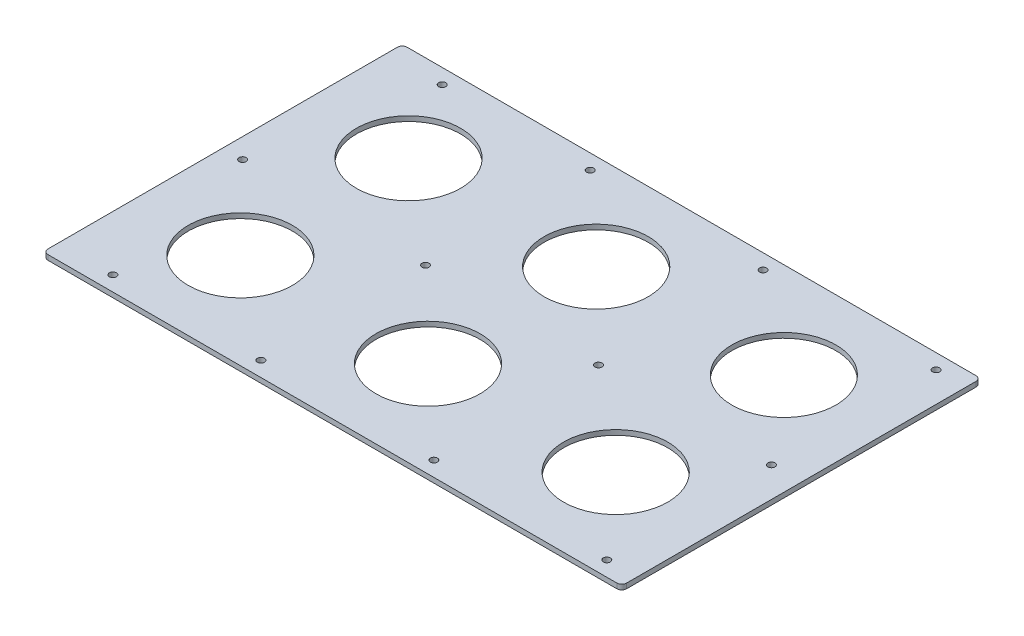
SolidWorks part; units mm, degrees
material "ABS"
ref_plane "Front" through (0, 0, 0) normal (0, 0, 1) x (1, 0, 0)
ref_plane "Top" through (0, 0, 0) normal (0, 1, 0) x (1, 0, 0)
ref_plane "Right" through (0, 0, 0) normal (1, 0, 0) x (0, 0, -1)
sketch "Sketch1" plane through (0, 0, 0) normal (0, 1, 0) x (1, 0, 0)
  line L1 (-180.975, 114.3) -> (180.975, 114.3)
  line L2 (-184.15, 111.125) -> (-184.15, -111.125)
  line L3 (-180.975, -114.3) -> (180.975, -114.3)
  line L4 (184.15, 111.125) -> (184.15, -111.125)
  line L5 (-184.15, 114.3) -> (184.15, -114.3) construction
  line L6 (-184.15, -114.3) -> (184.15, 114.3) construction
  circle A0 centre (119.5086, -53.5178) radius 33.147
  arc A1 (-184.15, -111.125) -> (-180.975, -114.3) centre (-180.975, -111.125) ccw
  arc A2 (180.975, -114.3) -> (184.15, -111.125) centre (180.975, -111.125) ccw
  arc A3 (184.15, 111.125) -> (180.975, 114.3) centre (180.975, 111.125) ccw
  arc A4 (-180.975, 114.3) -> (-184.15, 111.125) centre (-180.975, 111.125) ccw
  circle A5 centre (165.1, 0) radius 2.2479 construction
  circle A6 centre (165.1, 0) radius 2.2479
  circle A7 centre (-171.45, 0) radius 2.2479 construction
  circle A8 centre (-171.45, 0) radius 2.2479
  circle A21 centre (-55.0333, 0) radius 2.2479 construction
  circle A22 centre (55.0333, 0) radius 2.2479 construction
  circle A23 centre (-55.0333, 0) radius 2.2479
  circle A24 centre (55.0333, 0) radius 2.2479
  circle A25 centre (119.5086, 53.5178) radius 33.147
  circle A26 centre (0.0643, 53.5178) radius 33.147
  circle A27 centre (0.0643, -53.5178) radius 33.147
  circle A28 centre (-119.38, 53.5178) radius 33.147
  circle A29 centre (-119.38, -53.5178) radius 33.147
  arc A34 (-143.7521, 103.8733) -> (-143.7521, 3.1623) centre (-119.38, 53.5178) ccw construction
  arc A35 (-24.3078, 103.8733) -> (-24.3078, 3.1623) centre (0.0643, 53.5178) ccw construction
  arc A36 (95.1365, 103.8733) -> (95.1365, 3.1623) centre (119.5086, 53.5178) ccw construction
  arc A37 (-143.7521, -3.1623) -> (-143.7521, -103.8733) centre (-119.38, -53.5178) ccw construction
  arc A38 (-24.3078, -3.1623) -> (-24.3078, -103.8733) centre (0.0643, -53.5178) ccw construction
  arc A39 (95.1365, -3.1623) -> (95.1365, -103.8733) centre (119.5086, -53.5178) ccw construction
  circle A40 centre (-149.225, -104.775) radius 2.2479 construction
  circle A41 centre (-55.0333, -104.775) radius 2.2479 construction
  circle A42 centre (55.0333, -104.775) radius 2.2479 construction
  circle A43 centre (165.1, -104.775) radius 2.2479 construction
  circle A44 centre (-149.225, 104.775) radius 2.2479 construction
  circle A45 centre (-55.0333, 104.775) radius 2.2479 construction
  circle A46 centre (55.0333, 104.775) radius 2.2479 construction
  circle A47 centre (165.1, 104.775) radius 2.2479 construction
  circle A48 centre (-149.225, -104.775) radius 2.2479
  circle A49 centre (-55.0333, -104.775) radius 2.2479
  circle A50 centre (55.0333, -104.775) radius 2.2479
  circle A51 centre (165.1, -104.775) radius 2.2479
  circle A52 centre (-149.225, 104.775) radius 2.2479
  circle A53 centre (-55.0333, 104.775) radius 2.2479
  circle A54 centre (55.0333, 104.775) radius 2.2479
  circle A55 centre (165.1, 104.775) radius 2.2479
  point P0 (0, 0)
  dimension "D3" = 66.294
  dimension "D4" = 3.175
  dimension "D1" = 368.3
  dimension "D2" = 228.6
extrude "Boss-Extrude1" add sketch "Sketch1" along normal blind 3.175
sketch "Sketch2" [suppressed] plane through (0, 3.175, 0) normal (0, 1, 0) x (1, 0, 0)
  line L0 (170.15, 30) -> (170.15, -30) construction
  line L1 (0, 0) -> (184.15, 0) construction
  line L2 (184.15, -111.125) -> (184.15, 111.125) construction
  text T0 "W" font "Stencil" height in points 30
  point P7 (170.15, 0)
  dimension "D1" = 14
  dimension "D2" = 60
extrude "Cut-Extrude1" [suppressed] cut sketch "Sketch2" against normal through all
sketch "Sketch3" [suppressed] plane through (0, 0, 0) normal (0, 1, 0) x (1, 0, 0)
  line L0 (564.5895, -114.2759) -> (564.5895, 114.3581)
  line L1 (-186.5909, 117.2946) -> (1032.6091, 117.2946)
  line L2 (-186.5909, 117.2946) -> (-186.5909, -492.3054)
  line L3 (-186.5909, -492.3054) -> (1032.6091, -492.3054)
  line L4 (1032.6091, 117.2946) -> (1032.6091, -492.3054)
  line L5 (184.5895, -114.2759) -> (-184.2953, -114.2759)
  line L6 (184.5895, -114.2759) -> (184.5895, 114.3581)
  line L7 (184.5895, 114.3581) -> (-184.2953, 114.3581)
  line L8 (-184.2953, -114.2759) -> (-184.2953, 114.3581)
  line L9 (564.5895, -114.2759) -> (195.7047, -114.2759)
  line L10 (195.7047, -114.2759) -> (195.7047, 114.3581)
  line L11 (564.5895, 114.3581) -> (195.7047, 114.3581)
  line L12 (944.5895, -114.2759) -> (944.5895, 114.3581)
  line L13 (944.5895, -114.2759) -> (575.7047, -114.2759)
  line L14 (575.7047, -114.2759) -> (575.7047, 114.3581)
  line L15 (944.5895, 114.3581) -> (575.7047, 114.3581)
  line L16 (564.5895, -364.2759) -> (564.5895, -135.6419)
  line L17 (564.5895, -364.2759) -> (195.7047, -364.2759)
  line L18 (195.7047, -364.2759) -> (195.7047, -135.6419)
  line L19 (564.5895, -135.6419) -> (195.7047, -135.6419)
  line L20 (944.5895, -364.2759) -> (944.5895, -135.6419)
  line L21 (944.5895, -364.2759) -> (575.7047, -364.2759)
  line L22 (575.7047, -364.2759) -> (575.7047, -135.6419)
  line L23 (944.5895, -135.6419) -> (575.7047, -135.6419)
  line L24 (184.5895, -364.2759) -> (184.5895, -135.6419)
  line L25 (184.5895, -364.2759) -> (-184.2953, -364.2759)
  line L26 (-184.2953, -364.2759) -> (-184.2953, -135.6419)
  line L27 (184.5895, -135.6419) -> (-184.2953, -135.6419)
  dimension "D1" = 1219.2
  dimension "D2" = 609.6
  dimension "D3" = 3
  dimension "D4" = 2
